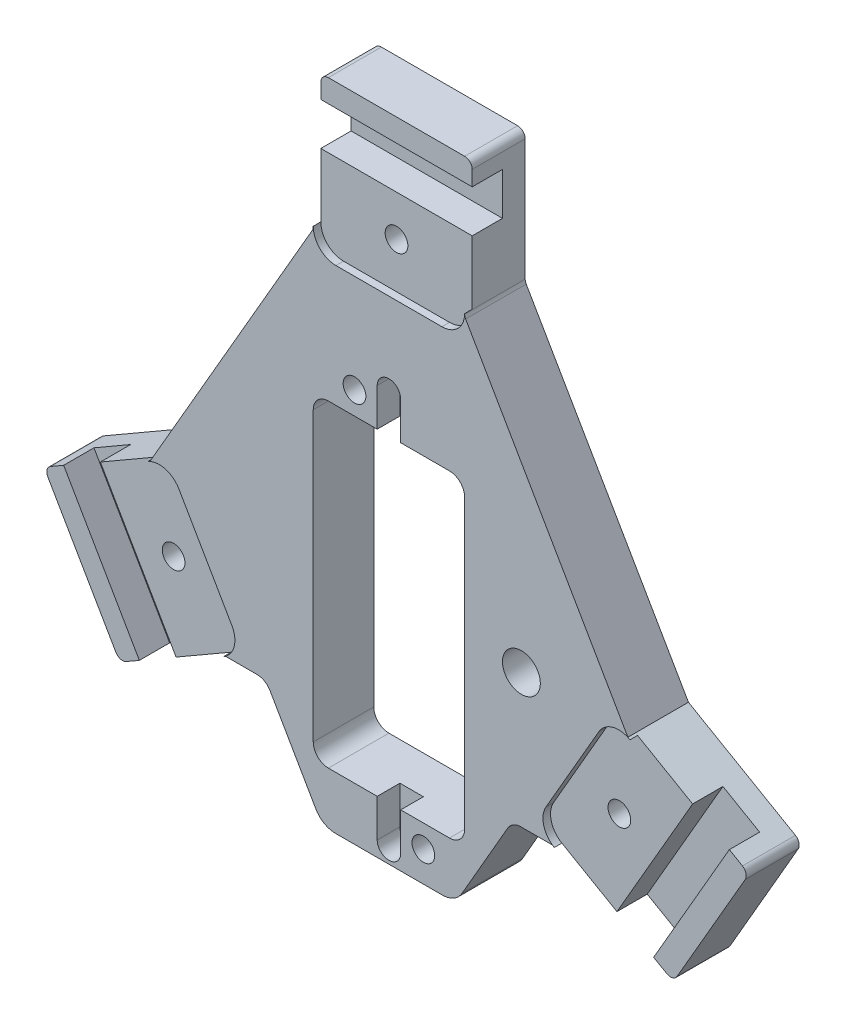
SolidWorks part; units mm, degrees
ref_plane "Front Plane" through (0, 0, 0) normal (0, 0, 1) x (1, 0, 0)
ref_plane "Top Plane" through (0, 0, 0) normal (0, 1, 0) x (1, 0, 0)
ref_plane "Right Plane" through (0, 0, 0) normal (1, 0, 0) x (0, 0, -1)
sketch "Sketch1" plane through (0, 0, 0) normal (0, 0, 1) x (1, 0, 0)
  line L4 (41.5692, -24) -> (32.909, -19) construction
  line L5 (-41.5692, -24) -> (-32.909, -19) construction
  line L7 (-10, 30.6795) -> (-10, 48)
  line L8 (10, 30.6795) -> (10, 48)
  line L9 (-10, 48) -> (10, 48)
  line L13 (21.5692, -24) -> (36.5692, -32.6603)
  line L14 (31.5692, -6.6795) -> (46.5692, -15.3397)
  line L15 (36.5692, -32.6603) -> (46.5692, -15.3397)
  line L16 (32.909, -19) -> (46.5692, -15.3397) construction
  line L17 (32.909, -19) -> (36.5692, -32.6603) construction
  line L19 (-21.5692, -24) -> (-36.5692, -32.6603)
  line L20 (-31.5692, -6.6795) -> (-46.5692, -15.3397)
  line L21 (-36.5692, -32.6603) -> (-46.5692, -15.3397)
  line L22 (-32.909, -19) -> (-46.5692, -15.3397) construction
  line L23 (-32.909, -19) -> (-36.5692, -32.6603) construction
  line L24 (-16.2785, -24) -> (-8.7952, -37)
  line L25 (-8.7952, -37) -> (8.7952, -37)
  line L26 (8.7952, -37) -> (16.2785, -24)
  line L27 (16.2785, -24) -> (21.5692, -24)
  line L28 (-10, 30.6795) -> (-31.5692, -6.6795)
  line L29 (-21.5692, -24) -> (-16.2785, -24)
  line L31 (31.5692, -6.6795) -> (10, 30.6795)
  point P10 (0, 38)
  point P12 (32.909, -19)
  point P17 (-32.909, -19)
  point P28 (0, -37)
  dimension "D3" = 20
  dimension "D6" = 20
  dimension "D8" = 20
  dimension "D12" = 15
  dimension "D13" = 15
extrude "Boss-Extrude1" add sketch "Sketch1" along normal blind 8
sketch "Sketch2" plane through (0, 0, 8) normal (0, 0, 1) x (1, 0, 0)
  line L0 (-41.5692, -24) -> (20.7846, 12) construction
  line L1 (-46.5692, -15.3397) -> (-36.5692, -32.6603) construction
  line L2 (31.5692, -6.6795) -> (10, 30.6795) construction
  line L3 (41.5692, -24) -> (-20.7846, 12) construction
  line L4 (36.5692, -32.6603) -> (46.5692, -15.3397) construction
  line L5 (-10, 30.6795) -> (-31.5692, -6.6795) construction
  line L6 (0, 48) -> (0, -37) construction
  line L7 (10, 48) -> (-10, 48) construction
  line L8 (-8.7952, -37) -> (8.7952, -37) construction
  line L9 (-36.5692, -32.6603) -> (-46.5692, -15.3397)
  line L10 (-7, 28) -> (7, 28)
  line L11 (-10, 31) -> (-10, 48)
  line L12 (-10, 48) -> (10, 48)
  line L13 (10, 31) -> (10, 48)
  line L14 (-10, 28) -> (10, 48) construction
  line L15 (-10, 48) -> (10, 28) construction
  line L16 (-36.5692, -32.6603) -> (-21.8468, -24.1603)
  line L17 (-46.5692, -15.3397) -> (-31.8468, -6.8397)
  line L18 (-20.7487, -20.0622) -> (-27.7487, -7.9378)
  line L19 (-36.5692, -32.6603) -> (-29.2487, -5.3397) construction
  line L20 (-46.5692, -15.3397) -> (-19.2487, -22.6603) construction
  line L21 (36.5692, -32.6603) -> (46.5692, -15.3397)
  line L22 (36.5692, -32.6603) -> (21.8468, -24.1603)
  line L23 (46.5692, -15.3397) -> (31.8468, -6.8397)
  line L24 (20.7487, -20.0622) -> (27.7487, -7.9378)
  line L25 (36.5692, -32.6603) -> (29.2487, -5.3397) construction
  line L26 (46.5692, -15.3397) -> (19.2487, -22.6603) construction
  arc A0 (-21.8468, -24.1603) -> (-20.7487, -20.0622) centre (-23.3468, -21.5622) ccw
  arc A1 (-27.7487, -7.9378) -> (-31.8468, -6.8397) centre (-30.3468, -9.4378) ccw
  arc A2 (21.8468, -24.1603) -> (20.7487, -20.0622) centre (23.3468, -21.5622) cw
  arc A3 (27.7487, -7.9378) -> (31.8468, -6.8397) centre (30.3468, -9.4378) cw
  arc A4 (10, 31) -> (7, 28) centre (7, 31) cw
  arc A5 (-7, 28) -> (-10, 31) centre (-7, 31) cw
  point P18 (0, 38)
  point P23 (-41.5692, -24)
  point P24 (-32.909, -19)
  point P25 (32.909, -19)
  point P26 (0, 48)
  point P37 (41.5692, -24)
  dimension "D7" = 3
  dimension "D1" = 20
  dimension "D2" = 20
  dimension "D3" = 20
  dimension "D4" = 20
  dimension "D5" = 20
  dimension "D6" = 20
extrude "Cut-Extrude1" cut sketch "Sketch2" against normal blind 1 contours L9 L16 A0 L18 A1 L17 | L21 L22 A2 L24 A3 L23 | L11 A5 L10 A4 L13 L12
sketch "Sketch3" plane through (0, 0, 7) normal (0, 0, 1) x (1, 0, 0)
  line L0 (0, 28) -> (0, 48) construction
  line L1 (-7, 28) -> (7, 28) construction
  line L2 (-10, 48) -> (10, 48) construction
  line L3 (24.2487, -14) -> (41.5692, -24) construction
  line L4 (20.7487, -20.0622) -> (27.7487, -7.9378) construction
  line L5 (36.5692, -32.6603) -> (46.5692, -15.3397) construction
  line L6 (-24.2487, -14) -> (-41.5692, -24) construction
  line L7 (-20.7487, -20.0622) -> (-27.7487, -7.9378) construction
  line L8 (-36.5692, -32.6603) -> (-46.5692, -15.3397) construction
  circle A0 centre (0, 34) radius 1.5
  circle A1 centre (29.4449, -17) radius 1.5
  circle A2 centre (-29.4449, -17) radius 1.5
  dimension "D2" = 3
  dimension "D3" = 3
  dimension "D6" = 3
  dimension "D1" = 14
  dimension "D4" = 14
  dimension "D5" = 14
extrude "Cut-Extrude2" cut sketch "Sketch3" against normal through all contours A0 | A1 | A2
sketch "Sketch4" plane through (0, 0, 7) normal (0, 0, 1) x (1, 0, 0)
  line L0 (-10, 45) -> (-10, 39.4)
  line L1 (-10, 45) -> (10, 45)
  line L2 (-10, 39.4) -> (10, 39.4)
  line L3 (10, 45) -> (10, 39.4)
  line L4 (-10, 31) -> (-10, 48) construction
  line L5 (39.1214, -11.0397) -> (43.9711, -13.8397)
  line L6 (39.1214, -11.0397) -> (29.1214, -28.3603)
  line L7 (43.9711, -13.8397) -> (33.9711, -31.1603)
  line L8 (29.1214, -28.3603) -> (33.9711, -31.1603)
  line L9 (46.5692, -15.3397) -> (31.8468, -6.8397) construction
  line L10 (-43.9711, -13.8397) -> (-39.1214, -11.0397)
  line L11 (-43.9711, -13.8397) -> (-33.9711, -31.1603)
  line L12 (-39.1214, -11.0397) -> (-29.1214, -28.3603)
  line L13 (-33.9711, -31.1603) -> (-29.1214, -28.3603)
  line L14 (-46.5692, -15.3397) -> (-31.8468, -6.8397) construction
  line L15 (-36.5692, -32.6603) -> (-21.8468, -24.1603) construction
  line L16 (36.5692, -32.6603) -> (21.8468, -24.1603) construction
  line L17 (10, 31) -> (10, 48) construction
  line L18 (-10, 48) -> (10, 48) construction
  line L19 (36.5692, -32.6603) -> (46.5692, -15.3397) construction
  line L20 (-36.5692, -32.6603) -> (-46.5692, -15.3397) construction
  dimension "D1" = 5.6
  dimension "D2" = 3
  dimension "D3" = 5.6
  dimension "D4" = 3
  dimension "D5" = 5.6
  dimension "D6" = 3
extrude "Cut-Extrude3" cut sketch "Sketch4" against normal blind 4
sketch "Sketch5" plane through (0, 0, 8) normal (0, 0, 1) x (1, 0, 0)
  line L0 (0, 28) -> (0, -37) construction
  line L1 (-7, 28) -> (7, 28) construction
  line L2 (-8.7952, -37) -> (8.7952, -37) construction
  line L3 (0, 12) -> (0, 17) construction
  line L4 (-8, -30) -> (-1.55, -30)
  line L5 (-10, -28) -> (-10, 10)
  line L6 (-8, 12) -> (-1.55, 12)
  line L7 (10, -28) -> (10, 10)
  line L8 (-10, -30) -> (10, 12) construction
  line L9 (-10, 12) -> (10, -30) construction
  line L10 (-1.55, 12) -> (-1.55, 17)
  line L11 (1.55, 12) -> (1.55, 17)
  line L12 (0, -30) -> (0, -35) construction
  line L13 (1.55, -30) -> (1.55, -35)
  line L14 (-1.55, -30) -> (-1.55, -35)
  line L15 (1.55, 12) -> (8, 12)
  line L16 (1.55, -30) -> (8, -30)
  line L17 (-1.55, 12) -> (1.55, 12)
  line L18 (-1.55, -30) -> (1.55, -30)
  line L19 (31.5692, -6.6795) -> (10, 30.6795) construction
  arc A0 (-8, -30) -> (-10, -28) centre (-8, -28) cw
  arc A1 (8, -30) -> (10, -28) centre (8, -28) ccw
  arc A2 (10, 10) -> (8, 12) centre (8, 10) ccw
  arc A3 (-10, 10) -> (-8, 12) centre (-8, 10) cw
  arc A5 (1.55, 17) -> (-1.55, 17) centre (0, 17) ccw
  arc A7 (-1.55, -35) -> (1.55, -35) centre (0, -35) ccw
  circle A8 centre (4.55, -33) radius 1.5
  circle A9 centre (-4.55, 15) radius 1.5
  circle A10 centre (17.5, -6.3109) radius 2.5
  point P6 (0, -9)
  point P25 (0, 14.5)
  point P30 (0, -32.5)
  dimension "D4" = 2
  dimension "D11" = 3
  dimension "D14" = 3
  dimension "D15" = 5
  dimension "D1" = 42
  dimension "D2" = 20
  dimension "D3" = 7
  dimension "D5" = 3.1
  dimension "D6" = 3.1
  dimension "D7" = 5
  dimension "D8" = 5
  dimension "D9" = 3
  dimension "D10" = 3
  dimension "D12" = 3
  dimension "D13" = 3
  dimension "D16" = 7.5
  dimension "D17" = 12
extrude "Cut-Extrude5" cut sketch "Sketch5" against normal through all contours A10 | A9 | A8 | A3 L5 A0 L4 L18 L16 A1 L7 A2 L15 L17 L6 region at (0, -9, 8) region at (4.55, -33, 8) region at (-4.55, 15, 8) region at (17.5, -6.3109, 8)
extrude "Cut-Extrude6" cut sketch "Sketch5<3>" against normal blind 3 contours L11 A5 L10 L17 | L14 A7 L13 L18 region at (0, -33.1183, 8) region at (0, 15.1183, 8)
sketch "Sketch5<3>" plane through (0, 0, 8) normal (0, 0, 1) x (1, 0, 0) same geometry as "Sketch5"
fillet "Fillet1" radius 1 6 edges at (10, 48, 3.5) (-10, 48, 3.5) (-36.5692, -32.6603, 3.5) (-46.5692, -15.3397, 3.5) (36.5692, -32.6603, 3.5) (46.5692, -15.3397, 3.5)
fillet "Fillet2" radius 3 2 edges at (-8.7952, -37, 4) (8.7952, -37, 4)
fillet "Fillet3" radius 2 2 edges at (16.2785, -24, 4) (-16.2785, -24, 4)
fillet "Fillet4" radius 1 1 edges at (10, 30.6795, 4)
fillet "Fillet6" radius 1 1 edges at (-10, 30.6795, 4)
